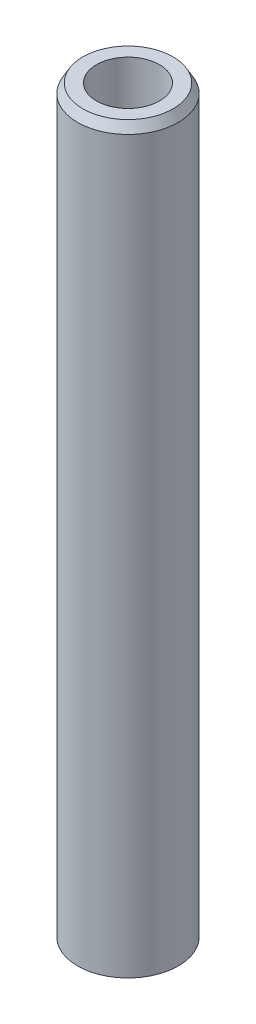
SolidWorks part; units mm, degrees
ref_plane "Front Plane" through (0, 0, 0) normal (0, 0, 1) x (1, 0, 0)
ref_plane "Top Plane" through (0, 0, 0) normal (0, 1, 0) x (1, 0, 0)
ref_plane "Right Plane" through (0, 0, 0) normal (1, 0, 0) x (0, 0, -1)
sketch "Sketch1" plane through (0, 0, 0) normal (0, 1, 0) x (1, 0, 0)
  circle A0 centre (0, 0) radius 12.5
  dimension "SHAFT_OD" = 25
extrude "Boss-Extrude1" add sketch "Sketch1" along normal blind 184.8826
sketch "Sketch2" plane through (0, 0, 0) normal (0, 1, 0) x (1, 0, 0)
  circle A0 centre (0, 0) radius 7.815
  dimension "BORE_D" = 15.63
extrude "Cut-Extrude1" cut sketch "Sketch2" along normal through all
chamfer "Chamfer1" distance 2.2702 angle 30 2 edges at (0, 184.8826, 12.5) (0, 0, 12.5) first distance on face at (0, 184.8826, 12.5) first distance on face at (0, 0, 7.815)
